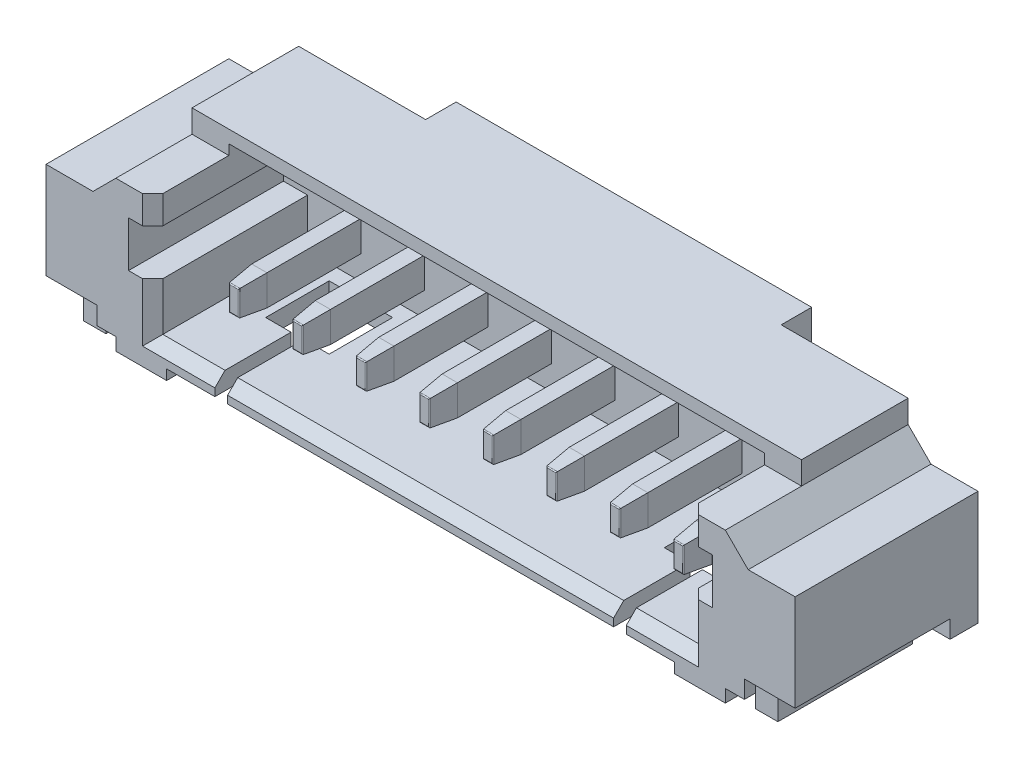
SolidWorks part; units mm, degrees
ref_plane "Front" through (0, 0, 0) normal (0, 0, 1) x (1, 0, 0)
ref_plane "Top" through (0, 0, 0) normal (0, 1, 0) x (1, 0, 0)
ref_plane "Right Side" through (0, 0, 0) normal (1, 0, 0) x (0, 0, -1)
sketch "Sketch1" plane through (0, 0, 0) normal (0, 0, 1) x (1, 0, 0)
  line L0 (0, 0) -> (0, 23.7826) construction
  line L1 (-7.375, 3.4) -> (7.375, 3.4)
  line L2 (-7.375, 3.4) -> (-7.375, 0)
  line L3 (-7.375, 0) -> (7.375, 0)
  line L4 (7.375, 3.4) -> (7.375, 0)
  dimension "D1" = 14.75
  dimension "D2" = 3.4
extrude "Main body" add sketch "Sketch1" along normal blind 3.05 and the other way blind 1.15
sketch "Sketch2" plane through (0, 0, 3.05) normal (0, 0, 1) x (1, 0, 0)
  line L0 (-7.375, 0.25) -> (-6, 0.25)
  line L1 (-7.375, 3.4) -> (-7.375, 0) construction
  line L2 (-6, 0.25) -> (-6, 0)
  line L3 (0, -3.2109) -> (0, 9.9619) construction
  line L4 (7.375, 0) -> (6, 0)
  line L5 (-7.375, 0) -> (7.375, 0) construction
  line L6 (-7.375, 0.25) -> (-7.375, 0)
  line L7 (-7.375, 0) -> (-6, 0)
  line L8 (7.375, 0.25) -> (7.375, 0)
  line L9 (6, 0.25) -> (6, 0)
  line L10 (7.375, 0.25) -> (6, 0.25)
  dimension "D1" = 0.25
  dimension "D2" = 12
extrude "Side notch-out detail" cut sketch "Sketch2" against normal through all
sketch "Sketch3" plane through (0, 0, 0) normal (0, 0, 1) x (1, 0, 0)
  line L0 (5.275, 2.4) -> (5.275, 2.95)
  line L1 (5.75, 2.4) -> (5.275, 2.4)
  line L2 (5.275, 2.95) -> (-5.275, 2.95)
  line L3 (0, 0.55) -> (0, 5.4944) construction
  line L4 (-5.275, 2.95) -> (-5.275, 2.4)
  line L5 (-5.275, 2.4) -> (-5.75, 2.4)
  line L6 (7.375, 3.4) -> (-7.375, 3.4) construction
  line L7 (-5.275, 1.5) -> (-5.275, 0.55)
  line L8 (-5.275, 0.55) -> (5.275, 0.55)
  line L9 (5.275, 0.55) -> (5.275, 1.5)
  line L10 (-6, 0) -> (6, 0) construction
  line L11 (-5.275, 1.5) -> (-5.75, 1.5)
  line L12 (-5.75, 1.5) -> (-5.75, 2.4)
  line L13 (5.75, 2.4) -> (5.75, 1.5)
  line L14 (5.75, 1.5) -> (5.275, 1.5)
  line L16 (-6, 0) -> (6, 0) construction
  dimension "D1" = 0.55
  dimension "D2" = 0.45
  dimension "D3" = 0.475
  dimension "D4" = 1.5
  dimension "D5" = 10.55
  dimension "D6" = 0.9
extrude "Main body recess" cut sketch "Sketch3" along normal through all
sketch "Sketch4" plane through (7.375, 0, 0) normal (1, 0, 0) x (0, 0, -1)
  line L0 (1.15, 0) -> (-3.05, 0) construction
  line L1 (-3.05, 0.6) -> (0, 0.6)
  line L4 (-3.05, 0.25) -> (-3.05, 3.4) construction
  line L8 (0, 0) -> (-3.05, 0)
  line L9 (0, 0) -> (0, 0.6)
  line L10 (-3.05, 0) -> (-3.05, 0.6)
  dimension "D1" = 0.6
  dimension "D2" = 3.05
extrude "Body notch-out for GND tab" cut sketch "Sketch4" against normal blind 1
mirror "Mirror5" about plane through (0, 0, 0) normal (1, 0, 0) of "Body notch-out for GND tab"
sketch "Sketch19" plane through (0, 3.4, 0) normal (0, 1, 0) x (-1, 0, 0)
  line L0 (7.375, 3.05) -> (7.375, -1.15) construction
  line L1 (7.375, -0.55) -> (7.375, -1.15)
  line L3 (-3.5, -1.15) -> (-3.5, -0.55)
  line L5 (-3.5, -1.15) -> (-7.375, -1.15)
  line L6 (-7.375, -0.55) -> (-7.375, -1.15)
  line L7 (-3.5, -0.55) -> (-7.375, -0.55)
  line L8 (3.5, -1.15) -> (3.5, -0.55)
  line L9 (3.5, -0.55) -> (7.375, -0.55)
  line L10 (3.5, -1.15) -> (7.375, -1.15)
  line L11 (0, 0) -> (0, -6.7503) construction
  dimension "D1" = 7
  dimension "D2" = 0.6
extrude "Vertical notch-out" cut sketch "Sketch19" against normal through all
sketch "Sketch20" plane through (0, 3.4, 0) normal (0, 1, 0) x (-1, 0, 0)
  line L1 (6, -0.55) -> (6, -1.15) construction
  line L2 (-7.375, 3.05) -> (7.375, 3.05) construction
  line L3 (-6, 3.05) -> (6, 3.05)
  line L6 (6, 3.05) -> (6, 2.05)
  line L8 (-6, -1.15) -> (-6, -0.55) construction
  line L10 (-6, 2.05) -> (-6, 3.05)
  line L12 (6, 2.05) -> (6.25, 2.05)
  line L13 (6.25, 2.05) -> (6.25, 1.55)
  line L14 (6.25, 1.55) -> (-6.25, 1.55)
  line L15 (-6.25, 1.55) -> (-6.25, 2.05)
  line L16 (-6.25, 2.05) -> (-6, 2.05)
  line L20 (0, 0) -> (0, 8.4) construction
  point P4 (0, 1.55)
  dimension "D1" = 1.5
  dimension "D2" = 1
  dimension "D3" = 12.5
extrude "Top surface relief" cut sketch "Sketch20" against normal blind 0.45
sketch "Sketch22" plane through (0, 0, 3.05) normal (0, 0, 1) x (1, 0, 0)
  line L0 (-6, 2.95) -> (-6, 3.4) construction
  line L1 (-7.375, 3.4) -> (-7.375, 0.6) construction
  line L2 (-6, 3.4) -> (-7.375, 3.4) construction
  line L3 (-7.375, 3.4) -> (-7.375, 2.5)
  line L4 (-6, 3.4) -> (-7.375, 3.4)
  line L5 (-6, 2.95) -> (-6, 3.4)
  line L6 (-6, 2.95) -> (-6.45, 2.5)
  line L7 (-6.45, 2.5) -> (-7.375, 2.5)
  line L8 (-6, 0) -> (6, 0) construction
  line L9 (0, -1.3039) -> (0, 6.7399) construction
  line L10 (6.45, 2.5) -> (7.375, 2.5)
  line L11 (6, 2.95) -> (6.45, 2.5)
  line L12 (6, 2.95) -> (6, 3.4)
  line L13 (6, 3.4) -> (7.375, 3.4)
  line L14 (7.375, 3.4) -> (7.375, 2.5)
  dimension "D1" = 2.5
  dimension "D2" = 135
extrude "Cut-Extrude1" cut sketch "Sketch22" against normal through all
sketch "Sketch21" plane through (0, 0, 0) normal (0, -1, 0) x (1, 0, 0)
  line L0 (0, -7.3265) -> (0, 10.8562) construction
  line L1 (-6.395, 0.2) -> (-6.835, 0.2)
  line L2 (-6.835, 0.2) -> (-6.835, 2.85)
  line L3 (-6.835, 2.85) -> (-6.395, 2.85)
  line L4 (-6.395, 2.85) -> (-6.395, 0.2)
  line L9 (6.395, 2.85) -> (6.395, 0.2)
  line L10 (6.835, 2.85) -> (6.395, 2.85)
  line L11 (6.835, 0.2) -> (6.835, 2.85)
  line L12 (6.395, 0.2) -> (6.835, 0.2)
  line L13 (-6.375, 0) -> (-6.375, 3.05) construction
  line L14 (-6.375, 3.05) -> (-7.375, 3.05) construction
  line L15 (-7.375, 0) -> (-6.375, 0) construction
  line L16 (-7.375, 0) -> (-7.375, 3.05) construction
  dimension "D1" = 0.02
  dimension "D2" = 0.2
  dimension "D3" = 0.2
  dimension "D4" = 0.54
extrude "Grounding tabs" add sketch "Sketch21" against normal up to surface (0.6 mm away) up to face at (-6.875, 0.6, 1.525)
ref_plane "Pin 1 X position plane" through (-5.655, 0, 0) normal (1, 0, 0) x (0, 0, -1)
ref_plane "Pin 1 c-s origin plane" through (0, 0, 2.35) normal (0, 0, -1) x (-1, 0, 0)
sketch "Sketch13" plane through (-5.655, 0, 0) normal (1, 0, 0) x (0, 0, -1)
  line L0 (-2.35, -1.87) -> (-2.35, 1.87) construction
  line L3 (2.25, 0.3) -> (1.65, 0.3)
  line L4 (1.65, 0.3) -> (1.65, 1.075)
  line L5 (1.15, 0) -> (0.55, 0) construction
  line L6 (1.15, 0) -> (1.15, 3.4) construction
  line L8 (1.15, 3.4) -> (1.15, 0) construction
  line L9 (-2.35, 1.375) -> (0.8, 1.375)
  line L10 (-0.2, 0) -> (-2.85, 0) construction
  line L12 (0.8, 1.375) -> (0.8, 1.075)
  line L13 (0.8, 1.075) -> (1.65, 1.075)
  dimension "D6" = 0.35
  dimension "D4" = 1.1
  dimension "D5" = 0.3
  dimension "D1" = 1.375
  dimension "D2" = 0.5
  dimension "D3" = 0.3
sketch "Sketch14" plane through (0, 0, 2.35) normal (0, 0, -1) x (-1, 0, 0)
  line L0 (6, 0) -> (-6, 0) construction
  line L1 (4.525, 1.625) -> (4.225, 1.025) construction
  line L2 (4.225, 1.625) -> (4.525, 1.025) construction
  line L3 (4.225, 1.625) -> (4.525, 1.625)
  line L4 (4.225, 1.625) -> (4.225, 1.025)
  line L5 (4.225, 1.025) -> (4.525, 1.025)
  line L6 (4.525, 1.625) -> (4.525, 1.025)
  line L7 (4.375, 1.325) -> (4.375, -0.4547) construction
  line L8 (0, 1.8485) -> (0, 0.55) construction
  line L9 (5.275, 1.5) -> (5.275, 0.55) construction
  line L10 (5.275, 0.55) -> (-5.275, 0.55) construction
  line L11 (0, 0.55) -> (0, 1.325) construction
  line L12 (0, 1.325) -> (-11.1524, 1.325) construction
  dimension "D1" = 0.3
  dimension "D2" = 0.6
  dimension "D3" = 0.9
  dimension "D4" = 1.325
sweep "Pin 1" add profiles "Sketch14" path "Sketch13"
chamfer "Pin 1 chamfer" distance 0.05 distance2 0.5 4 edges at (-4.375, 1.025, 2.35) (-4.525, 1.325, 2.35) (-4.375, 1.625, 2.35) (-4.225, 1.325, 2.35)
fillet "Pin 1 edge break" radius 0.02 4 edges at (-4.375, 1.575, 2.35) (-4.275, 1.325, 2.35) (-4.375, 1.075, 2.35) (-4.475, 1.325, 2.35)
chamfer "Pin 1 solder fillet chamfer" distance 0.2 angle 45 2 edges at (-4.375, -0.05, -2.25) (-4.375, -0.05, -1.3)
pattern_linear "All pins" count 8 spacing 1.25 along (1, 0, 0) of "Pin 1", "Pin 1 chamfer", "Pin 1 edge break", "Pin 1 solder fillet chamfer"
sketch "Sketch23" plane through (0, 0, 0) normal (0, -1, 0) x (1, 0, 0)
  line L1 (6, -0.55) -> (6, 3.05) construction
  line L4 (-6, 3.05) -> (6, 3.05) construction
  line L5 (6, 0.1) -> (6, 1.8)
  line L6 (-5, 3.05) -> (5, 3.05)
  line L7 (-6, -0.55) -> (-6, 3.05) construction
  line L8 (5, 3.05) -> (5, 1.8)
  line L9 (5, 1.8) -> (6, 1.8)
  line L10 (5, 0.1) -> (6, 0.1)
  line L11 (5, 0.1) -> (5, -1.15)
  line L12 (-6, 0.1) -> (-5, 0.1)
  line L13 (-5, 0.1) -> (-5, -1.15)
  line L14 (-6, 1.8) -> (-5, 1.8)
  line L15 (-5, 1.8) -> (-5, 3.05)
  line L16 (-5, -1.15) -> (5, -1.15)
  line L17 (-6, 0.1) -> (-6, 1.8)
  line L18 (-3.5, -1.15) -> (3.5, -1.15) construction
  dimension "D1" = 1.25
  dimension "D2" = 1
extrude "Bottom relief" cut sketch "Sketch23" against normal blind 0.2
sketch "Sketch24" plane through (0, 0, 0) normal (0, -1, 0) x (1, 0, 0)
  line L0 (-4.525, 0) -> (-4.525, 1.85) construction
  line L1 (-4.525, 0) -> (-4.525, 1.85) construction
  line L2 (5, 3.05) -> (-5, 3.05) construction
  line L3 (-3.3, 0.3) -> (-4.55, 0.3)
  line L4 (-4.55, 1.55) -> (-4.05, 1.55)
  line L5 (-3.8, 1.55) -> (-3.3, 1.55)
  line L6 (-3.8, 1.55) -> (-3.8, 3.05)
  line L7 (-3.8, 3.05) -> (-4.05, 3.05)
  line L9 (-3.925, 0.3) -> (-3.925, 4.5601) construction
  line L10 (0, -3.3328) -> (0, 9.2105) construction
  line L12 (-4.05, 1.55) -> (-4.05, 3.05)
  line L13 (-3.3, 1.55) -> (-3.3, 0.3)
  line L14 (-4.55, 1.55) -> (-4.55, 0.3)
  dimension "D1" = 0.25
  dimension "D2" = 1.5
  dimension "D3" = 1.25
  dimension "D4" = 1.25
  dimension "D5" = 0.6
extrude "Bottom locking feature" cut sketch "Sketch24" against normal blind 1
mirror "Mirror6" about plane through (0, 0, 0) normal (1, 0, 0) of "Bottom locking feature"
chamfer "Lead-in for mating part" distance 0.2 distance2 0.2 8 edges at (-5.275, 1.025, 3.05) (-4.6625, 0.55, 3.05) (0, 0.55, 3.05) (5.275, 2.675, 3.05) (4.6625, 0.55, 3.05) (5.275, 1.025, 3.05) (-5.275, 2.675, 3.05) (0, 2.95, 1.55)
